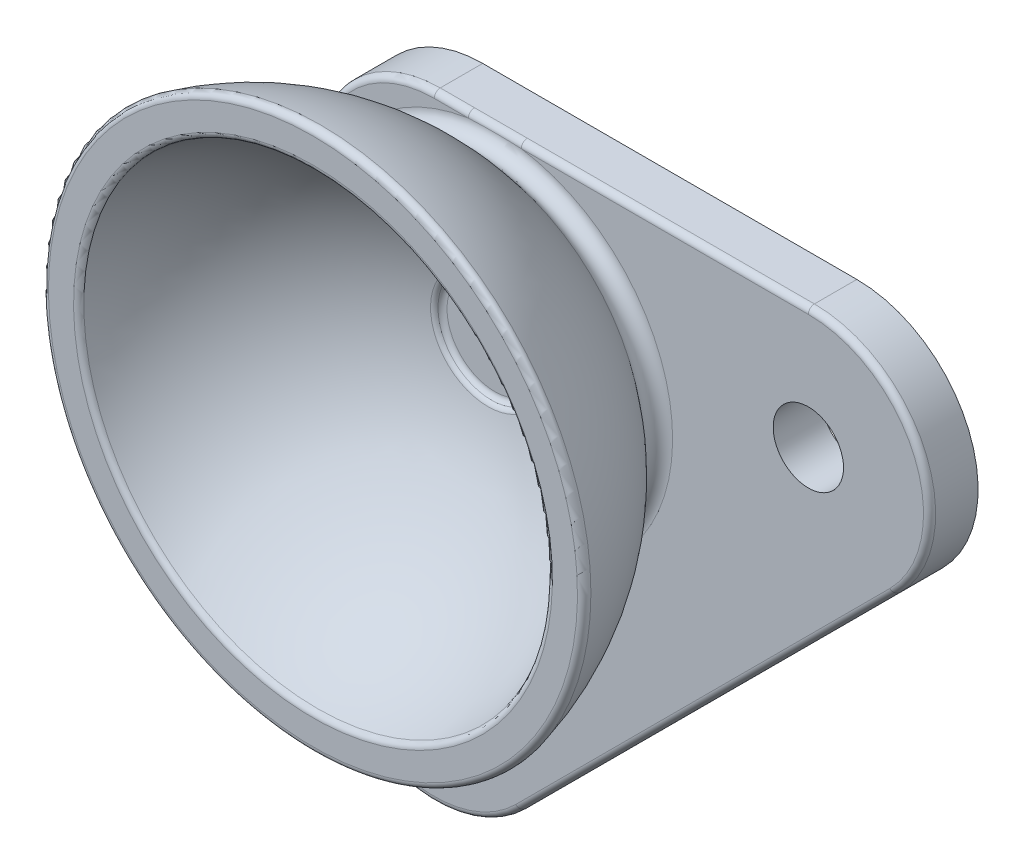
SolidWorks part; units mm, degrees
ref_plane "Front Plane" through (0, 0, 0) normal (0, 0, 1) x (1, 0, 0)
ref_plane "Top Plane" through (0, 0, 0) normal (0, 1, 0) x (1, 0, 0)
ref_plane "Right Plane" through (0, 0, 0) normal (1, 0, 0) x (0, 0, -1)
sketch "Sketch1" plane through (0, 0, 0) normal (0, 0, 1) x (1, 0, 0)
  line L0 (0, 0) -> (65, 0)
  line L1 (65, 0) -> (0, -65)
  line L2 (0, -65) -> (0, 0)
  dimension "D1" = 45
  dimension "D2" = 65
extrude "Boss-Extrude1" add sketch "Sketch1" along normal blind 4
ref_plane "Plane1" through (15, 0, 0) normal (1, 0, 0) x (0, 0, -1)
sketch "Sketch2" plane through (15, 0, 0) normal (1, 0, 0) x (0, 0, -1)
  line L0 (-4, -65) -> (-4, 0) construction
  line L1 (-19, -37.4499) -> (-19, -34.3649)
  line L2 (-4, -26.3578) -> (-4, -19.4441)
  line L4 (-4, -19.4441) -> (-4.5, -19.4441)
  line L5 (-4, -15) -> (-14.2815, -15) construction
  line L6 (-4, 0) -> (0, 0) construction
  arc A1 (-4, -26.3578) -> (-19, -37.4499) centre (-24, -15) cw
  arc A2 (-19, -34.3649) -> (-4.5, -19.4441) centre (-24, -15) ccw
  arc A3 (-4.5, -19.4441) -> (-4, -15) centre (-24, -15) ccw construction
  dimension "D1" = 0.5
  dimension "D2" = 20
  dimension "D3" = 3
  dimension "D4" = 15
  dimension "D5" = 15
revolve "Revolve2" add sketch "Sketch2" angle 360 about L5
hole_wizard "M5 Clearance Hole1" positions "Sketch3" profile "Sketch4" hole size "M5" standard "ANSI Metric" end condition through all
sketch "Sketch3" plane through (0, 0, 4) normal (0, 0, 1) x (1, 0, 0)
  line L0 (0, 0) -> (0, -65) construction
  line L1 (65, 0) -> (0, 0) construction
  line L2 (0, -65) -> (65, 0) construction
  point P0 (10, -40.8579)
  point P2 (40.8579, -10)
  dimension "D1" = 10
  dimension "D2" = 10
  dimension "D3" = 10
  dimension "D4" = 10
sketch "Sketch4" plane through (10, -40.8579, 4) normal (1, 0, 0) x (0, -1, 0)
  line L0 (0, 0) -> (0, 4)
  line L1 (0, 4) -> (2.9, 4)
  line L2 (2.9, 4) -> (2.9, 0)
  line L5 (2.9, 0) -> (0, 0)
  line L11 (0, -6.35) -> (0, 107.95) construction
  dimension "Thru Hole Dia." = 5.8
  dimension "Thru Hole Depth" = 4
sketch "Sketch6" plane through (0, 0, 4) normal (0, 0, 1) x (1, 0, 0)
  line L0 (0, -65) -> (65, 0) construction
  line L1 (0, 0) -> (0, -65) construction
  line L4 (0, -40.8579) -> (0, -65)
  line L5 (0, -65) -> (17.0711, -47.9289)
  arc A0 (17.0711, -47.9289) -> (0, -40.8579) centre (10, -40.8579) cw
extrude "Cut-Extrude1" cut sketch "Sketch6" against normal through all
sketch "Sketch7" plane through (0, 0, 4) normal (0, 0, 1) x (1, 0, 0)
  line L0 (65, 0) -> (0, 0) construction
  line L1 (17.0711, -47.9289) -> (65, 0) construction
  line L2 (40.8579, 0) -> (65, 0)
  line L3 (65, 0) -> (47.9289, -17.0711)
  arc A0 (40.8579, 0) -> (47.9289, -17.0711) centre (40.8579, -10) cw
extrude "Cut-Extrude2" cut sketch "Sketch7" against normal through all
fillet "Fillet1" radius 10 1 edges at (0, 0, 2)
fillet "Fillet2" radius 1 1 edges at (3.6422, -15, 4)
fillet "Fillet3" radius 0.5 1 edges at (10.5559, -15, 4)
fillet "Fillet4" radius 0.5 3 edges at (15, -10.5559, 4.5) (15, 4.3649, 19) (15, 7.4499, 19)
fillet "Fillet5" radius 0.5 6 edges at (2.9289, -2.9289, 4) (25.4289, 0, 4) (50.0967, -6.1732, 4) (32.5, -32.5, 4) (6.1732, -50.0967, 4) (0, -25.4289, 4)
